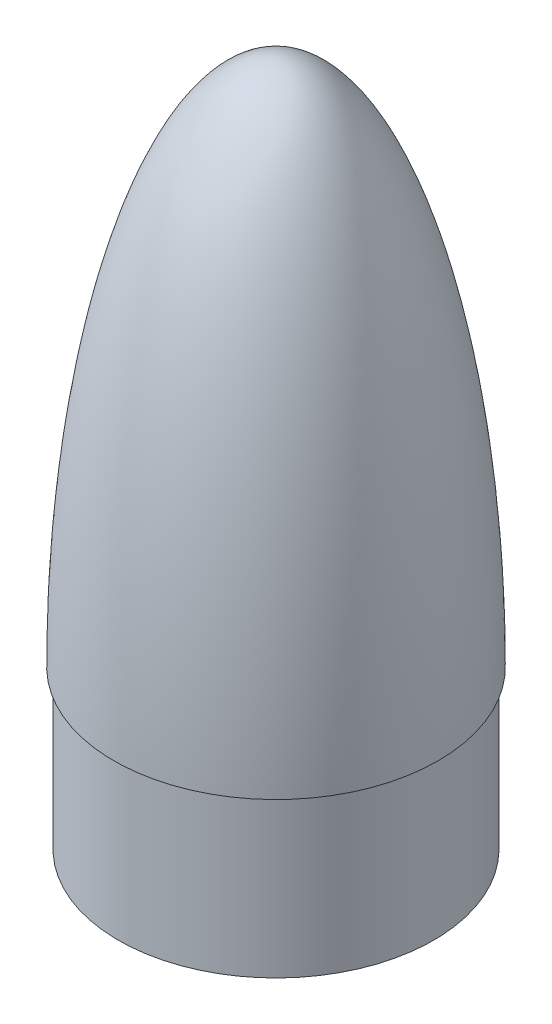
SolidWorks part; units mm, degrees
material "ABS"
ref_plane "Front Plane" through (0, 0, 0) normal (0, 0, 1) x (1, 0, 0)
ref_plane "Top Plane" through (0, 0, 0) normal (0, 1, 0) x (1, 0, 0)
ref_plane "Right Plane" through (0, 0, 0) normal (1, 0, 0) x (0, 0, -1)
sketch "Sketch1" plane through (0, 0, 0) normal (0, 0, 1) x (1, 0, 0)
  line L0 (0, 254) -> (0, 0) construction
  line L1 (78.359, 0) -> (0, 0)
  line L2 (0, 0) -> (0, 254)
  spline S0 degree 4 poles (77.9662, -25.3999) (78.0154, -23.8095) (78.1056, -20.6522) (78.1976, -16.6458) (78.2773, -11.9379) (78.3233, -7.8867) (78.3478, -4.9036) (78.3593, -1.4843) (78.3601, 0.7911) (78.3527, 3.5863) (78.3388, 5.9889) (78.318, 8.3522) (78.2903, 10.7456) (78.247, 13.7314) (78.1811, 17.3117) (78.0839, 21.4904) (77.9448, 26.2641) (77.7777, 31.0376) (77.5823, 35.8096) (77.3585, 40.5805) (77.0429, 46.5423) (76.6791, 52.5014) (76.2664, 58.4574) (75.8041, 64.4096) (75.404, 69.1689) (74.8656, 75.1148) (74.1574, 82.244) (73.2383, 90.5517) (72.0557, 100.0308) (70.7355, 109.4917) (69.2709, 118.9313) (67.25, 130.6999) (64.5017, 144.7638) (61.3086, 158.736) (57.591, 172.5772) (53.383, 186.2759) (49.2387, 198.0448) (44.4832, 209.5873) (38.9429, 220.7192) (34.2562, 228.6936) (29.8187, 235.0954) (25.6242, 240.1829) (21.9789, 243.9262) (18.5702, 246.8595) (15.4743, 249.0762) (12.5634, 250.7857) (9.7723, 252.0835) (7.0631, 253.0286) (4.2754, 253.6868) (2.188, 253.9399) (0.7672, 253.9999) (0, 254) knots 0 0 0 0 0 0.020823 0.041645 0.052056 0.062468 0.072879 0.08329 0.09112 0.098949 0.106779 0.114608 0.122438 0.130267 0.145926 0.161585 0.177244 0.192903 0.208562 0.224221 0.23988 0.271198 0.286857 0.302516 0.318175 0.333834 0.365152 0.39647 0.427788 0.459106 0.490424 0.521742 0.584379 0.647015 0.678333 0.709651 0.772287 0.810589 0.841907 0.872608 0.893486 0.912628 0.928287 0.941045 0.952387 0.962498 0.972496 0.981349 0.98995 1 1 1 1 1 construction
  spline S1 degree 4 poles (78.359, 0) (78.359, 0.5473) (78.3578, 1.6496) (78.3527, 3.5863) (78.3388, 5.9889) (78.318, 8.3522) (78.2903, 10.7456) (78.247, 13.7314) (78.1811, 17.3117) (78.0839, 21.4904) (77.9448, 26.2641) (77.7777, 31.0376) (77.5823, 35.8096) (77.3585, 40.5805) (77.0429, 46.5423) (76.6791, 52.5014) (76.2664, 58.4574) (75.8041, 64.4096) (75.404, 69.1689) (74.8656, 75.1148) (74.1574, 82.244) (73.2383, 90.5517) (72.0557, 100.0308) (70.7355, 109.4917) (69.2709, 118.9313) (67.25, 130.6999) (64.5017, 144.7638) (61.3086, 158.736) (57.591, 172.5772) (53.383, 186.2759) (49.2387, 198.0448) (44.4832, 209.5873) (38.9429, 220.7192) (34.2562, 228.6936) (29.8187, 235.0954) (25.6242, 240.1829) (21.9789, 243.9262) (18.5702, 246.8595) (15.4743, 249.0762) (12.5634, 250.7857) (9.7723, 252.0835) (7.0631, 253.0286) (4.2754, 253.6868) (2.188, 253.9399) (0.7672, 253.9999) (0, 254) knots 0.08329 0.08329 0.08329 0.08329 0.08329 0.09112 0.098949 0.106779 0.114608 0.122438 0.130267 0.145926 0.161585 0.177244 0.192903 0.208562 0.224221 0.23988 0.271198 0.286857 0.302516 0.318175 0.333834 0.365152 0.39647 0.427788 0.459106 0.490424 0.521742 0.584379 0.647015 0.678333 0.709651 0.772287 0.810589 0.841907 0.872608 0.893486 0.912628 0.928287 0.941045 0.952387 0.962498 0.972496 0.981349 0.98995 1 1 1 1 1
revolve "Revolve1" add sketch "Sketch1" angle 360 about L0
sketch "Sketch2" plane through (0, 0, 0) normal (0, -1, 0) x (1, 0, 0)
  circle A0 centre (0, 0) radius 76.2
extrude "Boss-Extrude1" add sketch "Sketch2" along normal blind 76.2
equation "\"Bodytube_OD\"= 6.17in"
equation "\"Bodytube_ID\"= 5.998in"
equation "\"R\"= \"Bodytube_ID\" / 2"
equation "\"L\"= 30in"
